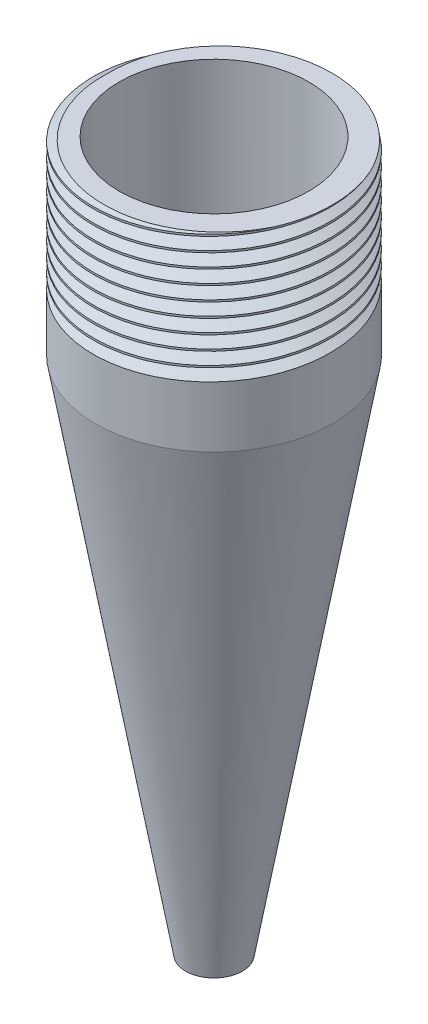
SolidWorks part; units mm, degrees
ref_plane "前视基准面" through (0, 0, 0) normal (0, 0, 1) x (1, 0, 0)
ref_plane "上视基准面" through (0, 0, 0) normal (0, 1, 0) x (1, 0, 0)
ref_plane "右视基准面" through (0, 0, 0) normal (1, 0, 0) x (0, 0, -1)
sketch "草图2" plane through (0, 0, 0) normal (0, 0, 1) x (1, 0, 0)
  line L1 (10, 0) -> (10, 30.4035) construction
  line L2 (1.5, 0.772) -> (10, 45.5566)
  line L6 (1.5, 0.772) -> (1.5, -9.228)
  line L9 (1.5, 0.772) -> (9.8938, 0.772) construction
  line L10 (10, 45.5566) -> (12.5, 45.5566)
  line L11 (12.5, 45.5566) -> (3, -9.228)
  line L12 (3, -9.228) -> (1.5, -9.228)
  line L13 (0, -20) -> (0, 58.9571) construction
  dimension "D1" = 10
  dimension "D2" = 1.5
  dimension "D4" = 10
  dimension "D5" = 2.5
  dimension "D6" = 1.5
revolve "旋转1" add sketch "草图2" angle 360 about L13
sketch "草图3" plane through (0, 45.5566, 0) normal (0, 1, 0) x (1, 0, 0)
  circle A0 centre (0, 0) radius 12.5
  circle A1 centre (0, 0) radius 10
  dimension "D1" = 20
  dimension "D2" = 25
extrude "凸台-拉伸1" add sketch "草图3" along normal blind 20
sketch "草图4" plane through (0, 65.5566, 0) normal (0, 1, 0) x (1, 0, 0)
  circle A0 centre (0, 0) radius 12.5
  dimension "D1" = 25
ref_plane "基准面1" through (-12.5, 0, 0) normal (1, 0, 0) x (0, 0, -1)
curve "螺旋线/涡状线1" pitch 1.5 height 13.5 radius 12.5 centre (0, 65.5566, 0) axis (0, -1, 0) start towards (-1, 0, 0)
sketch "草图6" plane through (0, 0, 0) normal (0, 0, 1) x (1, 0, 0)
  line L0 (12.5, 65.5566) -> (-12.5, 65.5566) construction
  line L4 (-11.375, 65.5566) -> (-12.5, 66.2061)
  line L5 (-12.5, 66.2061) -> (-12.5, 64.9071)
  line L6 (-12.5, 64.9071) -> (-11.375, 65.5566)
  line L7 (-12.5, 65.5566) -> (-12.5, 45.5566) construction
  circle A1 centre (-12.125, 65.5566) radius 0.375 construction
  dimension "D1" = 0.75
sweep "切除-扫描3" cut profiles "草图6" path "螺旋线/涡状线1" align with end faces yes
